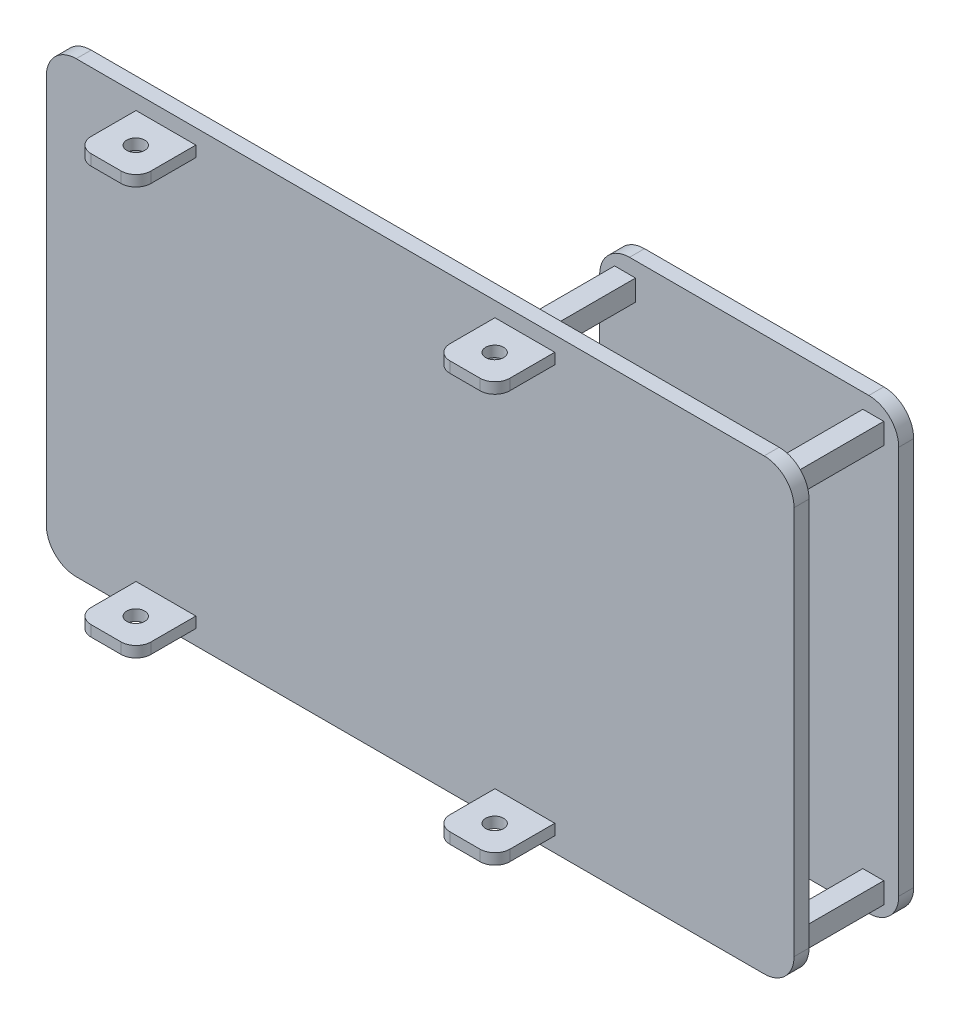
SolidWorks part; units mm, degrees
ref_plane "Front Plane" through (0, 0, 0) normal (0, 0, 1) x (1, 0, 0)
ref_plane "Top Plane" through (0, 0, 0) normal (0, 1, 0) x (1, 0, 0)
ref_plane "Right Plane" through (0, 0, 0) normal (1, 0, 0) x (0, 0, -1)
sketch "Sketch1" plane through (0, 0, 0) normal (0, 0, 1) x (1, 0, 0)
  line L0 (200, 150) -> (250, 150)
  line L1 (0, 0) -> (200, 0)
  line L2 (0, 0) -> (0, 150)
  line L3 (0, 150) -> (200, 150)
  line L21 (150, 5) -> (150, 8.6335)
  line L22 (150, 5) -> (170, 5)
  line L23 (50, 145) -> (30, 145)
  line L24 (50, 145) -> (50, 141.3665)
  line L25 (50, 141.3665) -> (30, 141.3665)
  line L26 (30, 145) -> (30, 141.3665)
  line L27 (150, 141.3665) -> (170, 141.3665)
  line L28 (170, 145) -> (170, 141.3665)
  line L29 (150, 145) -> (170, 145)
  line L30 (150, 145) -> (150, 141.3665)
  line L31 (170, 5) -> (170, 8.6335)
  line L32 (150, 8.6335) -> (170, 8.6335)
  line L33 (50, 8.6335) -> (30, 8.6335)
  line L34 (30, 5) -> (30, 8.6335)
  line L35 (50, 5) -> (30, 5)
  line L36 (50, 5) -> (50, 8.6335)
  line L37 (250, 150) -> (250, 0)
  line L38 (250, 0) -> (200, 0)
  point P10 (100, 150)
  point P13 (100, 0)
  dimension "D1" = 150
  dimension "D2" = 200
  dimension "D3" = 50
  dimension "D4" = 20
  dimension "D5" = 50
  dimension "D6" = 50
  dimension "D7" = 20
  dimension "D8" = 20
  dimension "D9" = 50
  dimension "D10" = 20
  dimension "D11" = 50
extrude "Boss-Extrude1" add sketch "Sketch1" along normal blind 5 contours L1 L3 L2 L36 L35 L34 L33 L30 L29 L28 L27 L26 L23 L24 L25 L21 L32 L31 L22 | L33 L34 L35 L36 | L32 L31 L22 L21 | L29 L28 L27 L30 | L23 L26 L25 L24 region at (125.1953, 75, 0)
extrude "Boss-Extrude2" add sketch "Sketch1<3>" along normal blind 25 contours L23 L26 L25 L24 | L35 L34 L33 L36 | L22 L31 L32 L21 | L29 L28 L27 L30
sketch "Sketch1<3>" plane through (0, 0, 0) normal (0, 0, 1) x (1, 0, 0) same geometry as "Sketch1"
sketch "Sketch2" plane through (0, 5, 0) normal (0, -1, 0) x (1, 0, 0)
  line L0 (170, 5) -> (150, 5) construction
  line L1 (30, 5) -> (50, 5) construction
  circle A0 centre (40, 15.1) radius 3
  circle A1 centre (160, 15.1) radius 3
  dimension "D3" = 6
  dimension "D4" = 6
  dimension "D1" = 10.1
  dimension "D2" = 10.1
extrude "Cut-Extrude1" cut sketch "Sketch2" against normal through all both and the other way through all
fillet "Fillet1" radius 5 8 edges at (30, 6.8167, 25) (50, 6.8167, 25) (150, 6.8167, 25) (170, 6.8167, 25) (170, 143.1833, 25) (150, 143.1833, 25) (50, 143.1833, 25) (30, 143.1833, 25)
fillet "Fillet2" radius 10 4 edges at (250, 150, 2.5) (250, 0, 2.5) (0, 150, 2.5) (0, 0, 2.5)
sketch "Sketch3" plane through (0, 0, 0) normal (0, 0, -1) x (-1, 0, 0)
  line L5 (-238, 145) -> (-245, 145)
  line L6 (-245, 12) -> (-245, 5)
  line L7 (-238, 5) -> (-245, 5)
  line L37 (-162, 5) -> (-162, 12)
  line L38 (-155, 12) -> (-162, 12)
  line L39 (-155, 5) -> (-155, 12)
  line L40 (-155, 5) -> (-162, 5)
  line L41 (-238, 5) -> (-238, 12)
  line L42 (-245, 12) -> (-238, 12)
  line L43 (-245, 5) -> (-245, 12)
  line L44 (-245, 5) -> (-238, 5)
  line L45 (-238, 145) -> (-238, 138)
  line L46 (-245, 138) -> (-238, 138)
  line L47 (-245, 145) -> (-245, 138)
  line L48 (-245, 145) -> (-238, 145)
  line L49 (-162, 145) -> (-162, 138)
  line L50 (-155, 138) -> (-162, 138)
  line L51 (-155, 145) -> (-155, 138)
  line L52 (-155, 145) -> (-162, 145)
  line L53 (-245, 145) -> (-245, 138)
  line L54 (-155, 5) -> (-162, 5)
  line L55 (-155, 145) -> (-155, 138)
  line L56 (-155, 145) -> (-162, 145)
  line L57 (-155, 12) -> (-155, 5)
extrude "Boss-Extrude3" add sketch "Sketch3" along normal blind 30 contours L51 L52 L49 L50 | L40 L39 L38 L37 | L42 L6 L7 L41 | L5 L47 L46 L45 region at (241.5, 141.5, 0) region at (241.5, 8.5, 0) region at (158.5, 8.5, 0) region at (158.5, 141.5, 0)
sketch "Sketch10" plane through (0, 0, -30) normal (0, 0, -1) x (-1, 0, 0)
  line L0 (-150, 150) -> (-150, 0)
  line L1 (-10, 150) -> (-240, 150) construction
  line L2 (-240, 0) -> (-10, 0) construction
  line L3 (-250, 140) -> (-250, 10) construction
  line L4 (-240, 0) -> (-150, 0)
  line L5 (-250, 140) -> (-250, 10)
  line L6 (-150, 150) -> (-240, 150)
  arc A0 (-250, 10) -> (-240, 0) centre (-240, 10) ccw construction
  arc A1 (-240, 150) -> (-250, 140) centre (-240, 140) ccw construction
  arc A2 (-250, 10) -> (-240, 0) centre (-240, 10) ccw
  arc A3 (-240, 150) -> (-250, 140) centre (-240, 140) ccw
  dimension "D1" = 100
extrude "Boss-Extrude5" add sketch "Sketch10" along normal blind 5
fillet "Fillet4" radius 10 2 edges at (150, 0, -32.5) (150, 150, -32.5)
